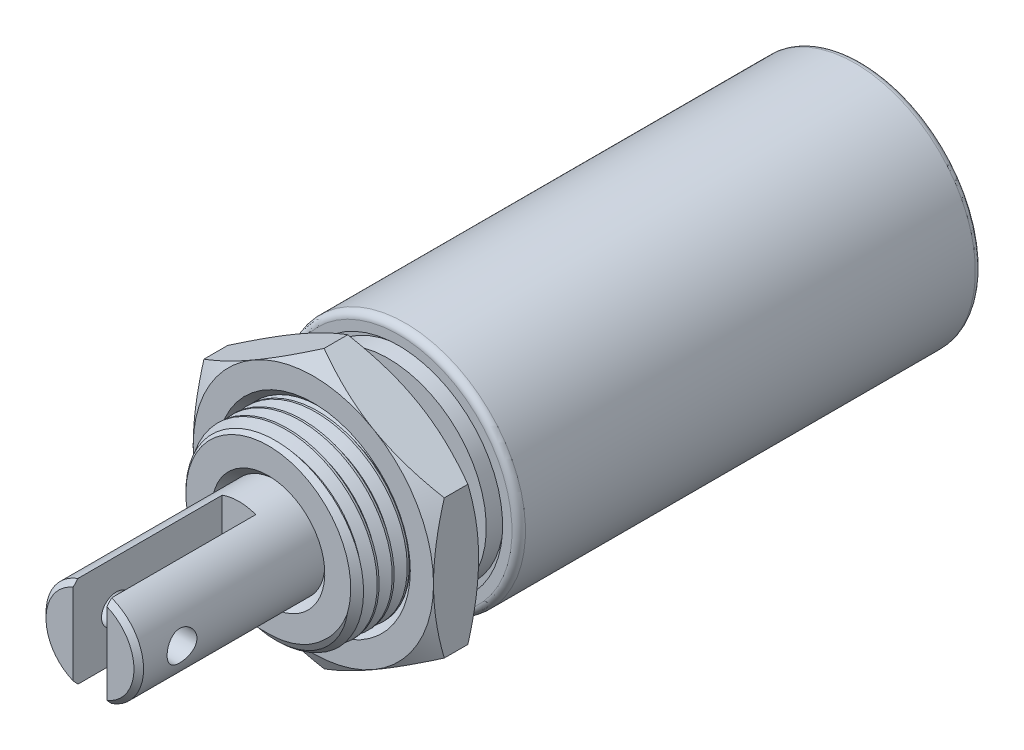
SolidWorks part; units mm, degrees
ref_plane "Front Plane" through (0, 0, 0) normal (0, 0, 1) x (1, 0, 0)
ref_plane "Top Plane" through (0, 0, 0) normal (0, 1, 0) x (1, 0, 0)
ref_plane "Right Plane" through (0, 0, 0) normal (1, 0, 0) x (0, 0, -1)
sketch "Sketch0" plane through (0, 0, 0) normal (1, 0, 0) x (0, 0, -1)
  line L0 (0, 0) -> (25.146, 0) construction
  line L1 (0, 0) -> (-15.7734, 0) construction
  line L2 (25.146, 6.35) -> (25.146, -6.35) construction
  line L3 (0, 4.7625) -> (0, -4.7625) construction
  line L4 (-15.7734, 2.5781) -> (-15.7734, -2.5781) construction
  line L5 (-15.7734, 0) -> (-22.1234, 0) construction
  point P10 (-13.4874, 0)
  point P12 (-6.35, 0)
  dimension "D1" = 13.4874
  dimension "Lg." = 25.146
  dimension "Dia." = 12.7
  dimension "Rod Dia." = 5.1562
  dimension "A" = 15.7734
  dimension "Thread OD" = 9.525
  dimension "Stroke" = 6.35
  dimension "D2" = 2.286
  dimension "D3" = 6.35
sketch "Sketch1" plane through (0, 0, 0) normal (1, 0, 0) x (0, 0, -1)
  line L0 (25.146, 0) -> (0, 0) construction
  line L1 (24.6634, 6.35) -> (0.889, 6.35)
  line L2 (25.146, 2.7432) -> (25.146, 0)
  line L3 (25.146, 0) -> (0, 0)
  line L4 (0.9144, 5.4991) -> (0.9144, 5.1689)
  line L5 (25.019, 2.8702) -> (25.019, 5.9944)
  line L6 (0.5334, 5.9944) -> (0.5334, 5.4991)
  line L7 (0.5334, 5.4991) -> (0.9144, 5.4991)
  line L8 (0.9144, 5.1689) -> (0, 5.1689)
  line L9 (0, 5.1689) -> (0, 0)
  arc A0 (25.146, 2.7432) -> (25.019, 2.8702) centre (25.019, 2.7432) ccw
  arc A1 (25.019, 5.9944) -> (24.6634, 6.35) centre (24.6634, 5.9944) ccw
  arc A2 (0.5334, 5.9944) -> (0.889, 6.35) centre (0.889, 5.9944) cw
  dimension "D1" = 0.3556
  dimension "D4" = 0.5334
  dimension "D2" = 0.127
  dimension "D3" = 5.4864
  dimension "D5" = 10.9982
  dimension "D6" = 0.381
  dimension "D7" = 10.3378
revolve "Revolve1" add sketch "Sketch1" angle 360 mid plane about L0
sketch "Sketch2" plane through (0, 0, 0) normal (1, 0, 0) x (0, 0, -1)
  line L0 (0, 0) -> (-15.7734, 0) construction
  line L3 (-6.35, 2.9845) -> (-6.35, 4.3561)
  line L4 (-6.35, 4.3561) -> (-5.9436, 4.7625)
  line L5 (-5.9436, 4.7625) -> (-1.2739, 4.7625)
  line L6 (-1.2739, 4.7625) -> (-0.8382, 4.1402)
  line L7 (-0.8382, 4.1402) -> (0, 4.1402)
  line L8 (0, 4.1402) -> (0, 2.5781)
  line L9 (-5.9436, 2.5781) -> (0, 2.5781)
  line L11 (-5.9436, 2.5781) -> (-6.35, 2.9845)
  dimension "D1" = 0.8382
  dimension "D4" = 0.4064
  dimension "D5" = 6.35
  dimension "D2" = 55
  dimension "D6" = 0.6223
  dimension "D3" = 45
  dimension "D8" = 0.4064
  dimension "D7" = 45
revolve "Revolve2" add sketch "Sketch2" angle 360 mid plane about L0
sketch "Sketch3" plane through (0, 0, 0) normal (1, 0, 0) x (0, 0, -1)
  line L0 (-15.7734, 0) -> (0, 0) construction
  line L1 (-15.5194, 2.5781) -> (-15.7734, 2.3241)
  line L2 (0, 0) -> (-15.7734, 0)
  line L3 (0, 0) -> (0, 2.5781)
  line L4 (0, 2.5781) -> (-15.5194, 2.5781)
  line L5 (-15.7734, 0) -> (-15.7734, 2.3241)
  line L6 (-15.5194, 2.5781) -> (-15.7734, 2.5781) construction
  line L7 (-15.7734, 2.5781) -> (-15.7734, 2.3241) construction
  dimension "D1" = 0.254
revolve "Revolve3" add sketch "Sketch3" angle 360 mid plane about L2
sketch "Sketch4" plane through (0, 0, 0) normal (0, 1, 0) x (0, 0, -1)
  line L1 (-15.7734, 0.889) -> (-7.8994, 0.889)
  line L2 (-15.7734, 0.889) -> (-15.7734, -0.889)
  line L3 (-15.7734, -0.889) -> (-7.8994, -0.889)
  line L4 (-7.8994, 0.889) -> (-7.8994, -0.889)
  dimension "D1" = 1.778
  dimension "D2" = 7.874
extrude "Cut-Extrude1" cut sketch "Sketch4" against normal up to surface and the other way up to surface up to face at (0, 2.5781, 15.5194) other way up to face at (0, 2.5781, 15.5194)
sketch "Sketch5" plane through (0, 0, 0) normal (1, 0, 0) x (0, -1, 0)
  line L0 (0, -15.7734) -> (0, -13.4874) construction
  circle A0 centre (0, -13.4874) radius 0.7874
  dimension "D1" = 1.5748
extrude "Cut-Extrude2" cut sketch "Sketch5" along normal up to surface and the other way up to surface up to face at (0, 0, 11.7094) other way up to face at (0, 0, 11.7094)
move or copy body "Body-Move/Copy1" bodies to move or copy 107 copy yes number of copies 1 translate (0, 0, 6.35)
sketch "SketchX" plane through (0, 0, 0) normal (1, 0, 0) x (0, 0, -1)
  line L0 (-21.8694, -2.42) -> (-14.2494, -2.42) construction
  line L1 (-22.1234, 2.1474) -> (-22.1234, -2.1474) construction
  line L2 (-21.8694, 2.42) -> (-14.2494, 2.42) construction
  line L7 (-14.2494, 2.5781) -> (-14.2494, 2.42) construction
  line L8 (-6.35, 2.5781) -> (-14.2494, 2.5781) construction
  line L11 (-14.2494, -2.42) -> (-14.2494, -2.5781) construction
  line L12 (-14.2494, -2.5781) -> (-6.35, -2.5781) construction
  line L13 (-21.8694, -2.42) -> (-14.2494, -2.42)
  line L14 (-22.1234, 2.1474) -> (-22.1234, -2.1474)
  line L15 (-21.8694, 2.42) -> (-14.2494, 2.42)
  line L16 (-14.2494, 2.5781) -> (-14.2494, 2.42)
  line L17 (-7.8994, 2.5781) -> (-14.2494, 2.5781)
  line L18 (-14.2494, -2.42) -> (-14.2494, -2.5781)
  line L19 (-14.2494, -2.5781) -> (-7.8994, -2.5781)
  line L20 (-7.8994, 2.5781) -> (-7.8994, 2.42) construction
  arc A1 (-22.1234, -2.1474) -> (-21.8694, -2.42) centre (12.7027, 30.0451) ccw construction
  circle A2 centre (-19.8374, 0) radius 0.7874 construction
  arc A3 (-21.8694, 2.42) -> (-22.1234, 2.1474) centre (12.7027, -30.0451) ccw construction
  arc A4 (-22.1234, -2.1474) -> (-21.8694, -2.42) centre (12.7027, 30.0451) ccw
  circle A5 centre (-19.8374, 0) radius 0.7874
  arc A6 (-21.8694, 2.42) -> (-22.1234, 2.1474) centre (12.7027, -30.0451) ccw
delete or keep bodies "Body-Delete1" type delete bodies bodies 108
sketch "Sketch10" plane through (0, 0, 0) normal (0, 0, 1) x (1, 0, 0)
  line L0 (0, 4.7625) -> (0, 6.35) construction
  line L1 (0, 7.3323) -> (-6.35, 3.6662)
  line L2 (-6.35, 3.6662) -> (-6.35, -3.6662)
  line L3 (-6.35, -3.6662) -> (0, -7.3323)
  line L4 (0, -7.3323) -> (6.35, -3.6662)
  line L5 (6.35, -3.6662) -> (6.35, 3.6662)
  line L6 (6.35, 3.6662) -> (0, 7.3323)
  circle A0 centre (0, 0) radius 4.7625
  circle A1 centre (0, 0) radius 6.35 construction
  dimension "D1" = 12.7
extrude "Boss-Extrude3" add sketch "Sketch10" along normal blind 2.3813 from offset 1.5875 separate body
sketch "Sketch11" plane through (0, 0, 0) normal (1, 0, 0) x (0, 0, -1)
  line L0 (-3.9688, 0) -> (-1.5875, 0) construction
  line L1 (-3.9688, 6.35) -> (-3.9688, 7.3323)
  line L2 (-3.9688, 3.6662) -> (-3.9688, 7.3323) construction
  line L3 (-3.9688, 7.3323) -> (-3.4016, 7.3323)
  line L4 (-3.4016, 7.3323) -> (-3.9688, 6.35)
  line L5 (-1.5875, 7.3323) -> (-2.1547, 7.3323)
  line L6 (-3.9688, 7.3323) -> (-1.5875, 7.3323) construction
  line L7 (-2.1547, 7.3323) -> (-1.5875, 6.35)
  line L8 (-1.5875, 3.6662) -> (-1.5875, 7.3323) construction
  line L9 (-1.5875, 6.35) -> (-1.5875, 7.3323)
  line L10 (-3.9688, 6.35) -> (0, 6.35) construction
  line L11 (-3.9688, 4.7625) -> (-3.9688, 5.1225)
  line L12 (-3.9688, 5.1225) -> (-3.6088, 4.7625)
  line L13 (-1.2739, 4.7625) -> (-5.9436, 4.7625) construction
  line L14 (-3.6088, 4.7625) -> (-3.9688, 4.7625)
  line L15 (-1.5875, -4.7625) -> (-1.5875, 4.7625) construction
  line L16 (-1.5875, 4.7625) -> (-1.9475, 4.7625)
  line L17 (-1.9475, 4.7625) -> (-1.5875, 5.1225)
  line L18 (-1.5875, 5.1225) -> (-1.5875, 4.7625)
  line L21 (-3.9688, 4.7625) -> (-3.9688, -4.7625) construction
  dimension "D1" = 30
revolve "Cut-Revolve1" cut sketch "Sketch11" angle 360 about L0
sketch "Sketch6" plane through (0, 0, 6.35) normal (0, 0, 1) x (1, 0, 0)
  circle A1 centre (0, 0) radius 4.7625
  point P1 (0, 4.7625)
curve "Helix/Spiral1" pitch 0.7937 height 6.3056 radius 4.7625 centre (0, 0, 6.35) axis (0, 0, -1) start towards (0, 1, 0) parameters "Pitch"=0.7937
sketch "Sketch7" plane through (0, 0, 0) normal (1, 0, 0) x (0, 0, -1)
  line L0 (-7.0941, 4.8484) -> (-6.3004, 4.8484) construction
  line L1 (-6.3004, 4.8484) -> (-6.6973, 4.161) construction
  line L2 (-6.6973, 4.161) -> (-7.0941, 4.8484) construction
  line L3 (-6.7469, 4.2469) -> (-6.6477, 4.2469) construction
  line L4 (-7.0445, 4.7625) -> (-6.35, 4.7625) construction
  line L5 (-6.6973, 4.161) -> (-6.6973, 4.2469) construction
  line L6 (-6.6973, 4.7625) -> (-6.6973, 4.8484) construction
  line L7 (-6.7469, 4.2469) -> (-6.6477, 4.2469)
  line L8 (-6.6477, 4.2469) -> (-6.3252, 4.8055)
  line L9 (-6.3252, 4.8055) -> (-7.0693, 4.8055)
  line L10 (-7.0693, 4.8055) -> (-6.7469, 4.2469)
  line L11 (-6.6973, 4.161) -> (-6.6973, -4.7625) construction
  line L12 (-6.6973, -4.7625) -> (-5.9035, -4.7625) construction
  line L13 (-5.9035, -4.7625) -> (-5.1098, -4.7625) construction
  line L14 (-5.1098, -4.7625) -> (-4.316, -4.7625) construction
  line L15 (-5.9436, -4.7625) -> (-1.2739, -4.7625) construction
  point P15 (-6.6973, 4.8055)
  dimension "D1" = 0.7937
  dimension "D2" = 0.0992
sweep "Cut-Sweep1" cut profiles "Sketch7" path "Helix/Spiral1"
equation "\"D3@Helix/Spiral1\" = \"Pitch@Helix/Spiral1\" + \"D5@Sketch2\" - \"D1@Sketch2\""
equation "\"D1@Sketch7\" = \"Pitch@Helix/Spiral1\""
equation "\"D2@Sketch7\" = \"D1@Sketch7\" / 8"
